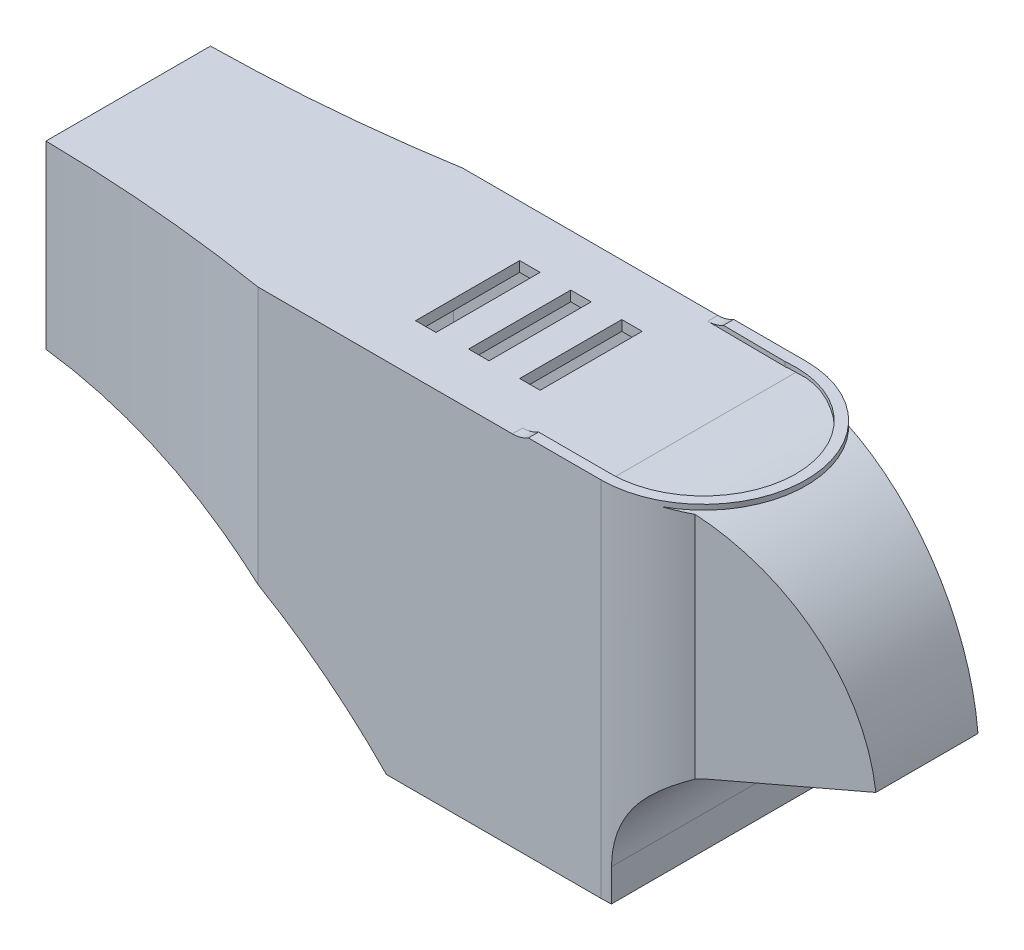
SolidWorks part; units mm, degrees
ref_plane "Front Plane" through (0, 0, 0) normal (0, 0, 1) x (1, 0, 0)
ref_plane "Top Plane" through (0, 0, 0) normal (0, 1, 0) x (1, 0, 0)
ref_plane "Right Plane" through (0, 0, 0) normal (1, 0, 0) x (0, 0, -1)
sketch "Sketch1" plane through (0, 0, 0) normal (0, 0, 1) x (1, 0, 0)
  line L4 (12, -14.2273) -> (12, -17.3873)
  line L5 (12, -17.3873) -> (-10, -17.3873)
  line L7 (1, 17.6627) -> (32.8741, 17.6627) construction
  line L11 (18.8003, -4.753) -> (32.8741, 0)
  line L13 (11, 17.6627) -> (-45.3259, 17.6627)
  line L14 (-45.3259, 17.6627) -> (-45.3259, 0)
  arc A3 (11, 17.6627) -> (32.8741, 0) centre (13.1057, -2.1057) cw
  arc A4 (-45.3259, 0) -> (-10, -17.3873) centre (-52.0942, -58.3308) cw
  arc A5 (18.8003, -4.753) -> (12, -14.2273) centre (22, -14.2273) ccw
  point P12 (1, -17.3873)
  dimension "D4" = 78.2
  dimension "D7" = 58.7221
  dimension "D3" = 10
  dimension "D1" = 22
  dimension "D5" = 35.05
  dimension "D8" = 17.6627
extrude "Boss-Extrude1" add sketch "Sketch1" against normal blind 20.1
sketch "Sketch5" plane through (0, 0, 0) normal (0, 1, 0) x (1, 0, 0)
  line L0 (-22.6095, 20.1) -> (-45.3259, 20.1)
  line L1 (-45.3259, 20.1) -> (-45.3259, 0) construction
  line L2 (-45.3259, 20.1) -> (-45.3259, 18.1)
  line L7 (-45.3259, 0) -> (-45.3259, 2)
  line L17 (-45.3259, 0) -> (-22.5473, 0)
  line L18 (11, 20.1) -> (-45.3259, 20.1) construction
  line L20 (-45.3259, 0) -> (-10, 0) construction
  arc A0 (-45.3259, 2) -> (-22.5473, 0) centre (-47.3699, -151.9965) cw
  arc A1 (-45.3259, 18.1) -> (-22.6095, 20.1) centre (-47.4369, 172.0855) ccw
  dimension "D8" = 2
  dimension "D9" = 2
extrude "Cut-Extrude5" cut sketch "Sketch5" along normal blind 28 and the other way blind 10
sketch "Sketch7" plane through (0, 0, 0) normal (0, 1, 0) x (1, 0, 0)
  line L0 (11, 20.1) -> (11, 0) construction
  line L1 (11, 20.1) -> (11, 0)
  line L2 (11, 10.05) -> (32.8741, 10.05) construction
  line L3 (32.8741, 20.1) -> (32.8741, 0) construction
  line L4 (32.8741, 10.05) -> (32.8741, 15.05)
  line L6 (32.8741, 10.05) -> (32.8741, 5.05)
  line L8 (11, 0) -> (32.8741, 0)
  line L9 (32.8741, 0) -> (32.8741, 5.05)
  line L10 (32.8741, 15.05) -> (32.8741, 20.1)
  line L11 (32.8741, 20.1) -> (11, 20.1)
  line L12 (17.6801, 17.5586) -> (32.8741, 15.05)
  line L13 (17.6841, 2.5449) -> (32.8741, 5.05)
  arc A1 (11, 0) -> (17.6841, 2.5449) centre (11, 10.05) ccw
  arc A4 (17.6801, 17.5586) -> (11, 20.1) centre (11, 10.05) ccw
  dimension "D3" = 15.1939
  dimension "D1" = 10
  dimension "D2" = 5
  dimension "D4" = 15.19
extrude "Cut-Extrude13" cut sketch "Sketch7" along normal blind 28 and the other way blind 28 contours A4 L10 L11 | A1 L8 L9 region at (25.2618, 0, -18.2368) region at (25.2609, 0, -1.8637)
shell "Shell6" thickness 1 removed face at (4.3335, -17.3873, -10.05) removed face at (-45.3259, 8.8313, -10.05) removed face at (-25.7684, -7.9133, -9.8549)
ref_plane "Plane5" through (0, 17.6, 0) normal (0, 1, 0) x (1, 0, 0)
sketch "Sketch8" plane through (0, 17.6, 0) normal (0, 1, 0) x (1, 0, 0)
  line L0 (11, 20.1) -> (11, 0) construction
  line L1 (11, 20.1) -> (3.8991, 20.1)
  line L2 (11, 20.1) -> (-22.6095, 20.1) construction
  line L3 (3.8991, 20.1) -> (3.8991, 19.1)
  line L4 (11, 0) -> (-45.3259, 0) construction
  line L5 (3.8991, 0) -> (11, 0)
  line L6 (3.8991, 1) -> (3.8991, 0)
  line L7 (3.8991, 1) -> (11, 1)
  line L8 (3.8991, 19.1) -> (10.006, 19.0453)
  arc A0 (11, 0) -> (11, 20.1) centre (11, 10.05) ccw
  arc A4 (11, 1) -> (10.006, 19.0453) centre (11, 10.05) ccw
  dimension "D1" = 1
  dimension "D2" = 1
extrude "Boss-Extrude2" add sketch "Sketch8" along normal blind 0.5
fillet "Fillet1" radius 3 1 edges at (3.8991, 17.6627, -19.6)
fillet "Fillet2" radius 3 1 edges at (3.8991, 17.6627, -0.5)
sketch "Sketch9" plane through (0, 0, 0) normal (0, 1, 0) x (1, 0, 0)
  line L2 (-2, 10.05) -> (-2, 15.05)
  line L3 (-2, 15.05) -> (0, 15.05)
  line L4 (0, 15.05) -> (0, 5.05)
  line L5 (0, 5.05) -> (-2, 5.05)
  line L6 (-2, 5.05) -> (-2, 10.05)
  line L7 (-5, 15.05) -> (-7, 15.05)
  line L8 (-7, 15.05) -> (-7, 5.05)
  line L9 (-7, 5.05) -> (-5, 5.05)
  line L10 (-5, 5.05) -> (-5, 15.05)
  line L11 (-10, 15.05) -> (-12, 15.05)
  line L12 (-12, 15.05) -> (-12, 4.8581)
  line L13 (-12, 4.8581) -> (-10, 4.8581)
  line L14 (-10, 4.8581) -> (-10, 15.05)
  dimension "D1" = 10
  dimension "D3" = 3
  dimension "D4" = 3
  dimension "D5" = 2
  dimension "D6" = 2
  dimension "D7" = 2
extrude "Cut-Extrude14" cut sketch "Sketch9" along normal blind 57
ref_plane "Plane4" through (0, 17.66, 0) normal (0, -1, 0) x (-1, 0, 0)
